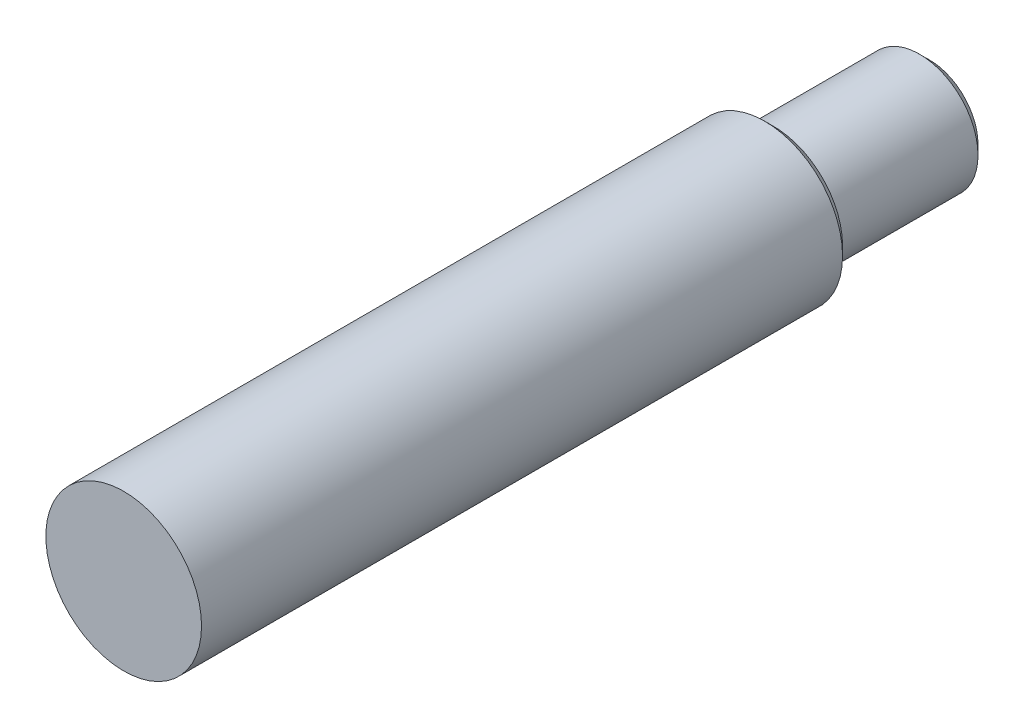
SolidWorks part; units mm, degrees
ref_plane "Front Plane" through (0, 0, 0) normal (0, 0, 1) x (1, 0, 0)
ref_plane "Top Plane" through (0, 0, 0) normal (0, 1, 0) x (1, 0, 0)
ref_plane "Right Plane" through (0, 0, 0) normal (1, 0, 0) x (0, 0, -1)
sketch "Sketch1" plane through (0, 0, 0) normal (1, 0, 0) x (0, 0, -1)
  line L0 (0, 0) -> (0, 4)
  line L1 (0, 4) -> (32.94, 4)
  line L2 (32.94, 4) -> (33.4, 3.54)
  line L3 (33.4, 3.54) -> (33.4, 3)
  line L4 (33.4, 3) -> (40.9, 3)
  line L5 (40.9, 3) -> (41.4, 2.5)
  line L6 (41.4, 2.5) -> (41.4, 0)
  line L7 (41.4, 0) -> (0, 0)
  line L8 (41.4, 0) -> (0, 0) construction
revolve "Revolve1" add sketch "Sketch1" angle 360 about L8 reverse direction yes
cosmetic thread "Cosmetic Thread1" parameters "D1"=8, "D2"=7.08
ref_plane "ANBAU XY" through (0, 0, 0) normal (0, 0, 1) x (1, 0, 0)
ref_plane "ANBAU XZ" through (0, 0, 0) normal (0, -1, 0) x (-1, 0, 0)
ref_plane "ANBAU YZ" through (0, 0, 0) normal (1, 0, 0) x (0, 0, -1)
ref_axis "ANBAU X" through (-80.9, 0, 0) along (1, 0, 0)
ref_axis "ANBAU Y" through (0, -50, 0) along (0, 1, 0)
ref_axis "ANBAU Z" through (0, 0, 80.9) along (0, 0, -1)
sketch3d "ANBAU"
  point P0 (0, 0, 0)
other "Freeze***"
